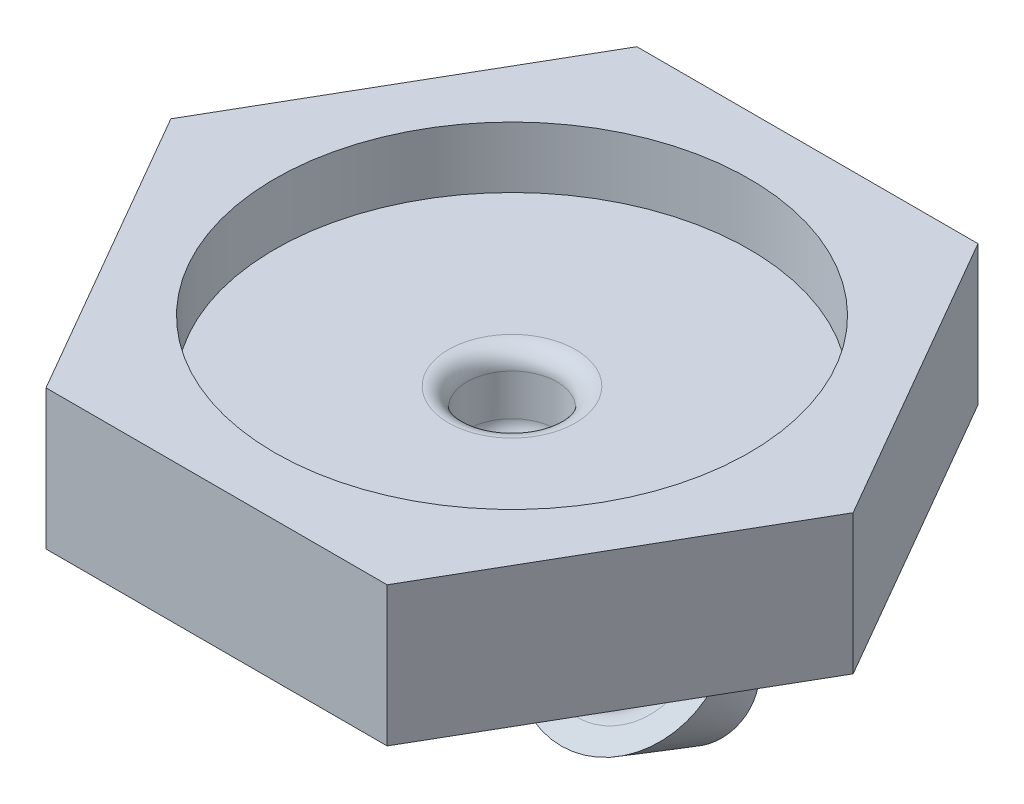
SolidWorks part; units mm, degrees
ref_plane "Front Plane" through (0, 0, 0) normal (0, 0, 1) x (1, 0, 0)
ref_plane "Top Plane" through (0, 0, 0) normal (0, 1, 0) x (1, 0, 0)
ref_plane "Right Plane" through (0, 0, 0) normal (1, 0, 0) x (0, 0, -1)
sketch "Sketch11" plane through (0, 0, 0) normal (0, 1, 0) x (1, 0, 0)
  line L7 (18.3309, 0) -> (9.1654, 15.875)
  line L8 (9.1654, 15.875) -> (-9.1654, 15.875)
  line L9 (-9.1654, 15.875) -> (-18.3309, 0)
  line L10 (-18.3309, 0) -> (-9.1654, -15.875)
  line L11 (-9.1654, -15.875) -> (9.1654, -15.875)
  line L12 (9.1654, -15.875) -> (18.3309, 0)
  circle A0 centre (0, 0) radius 15.875 construction
  dimension "D1" = 31.75
extrude "MainHolder" add sketch "Sketch11" along normal blind 7.5
sketch "Sketch12" plane through (0, 7.5, 0) normal (0, 1, 0) x (1, 0, 0)
  circle A0 centre (0, 0) radius 12.75
  dimension "D1" = 25.5
extrude "MagnetCutout" cut sketch "Sketch12" against normal blind 3.28
sketch "Sketch13" plane through (0, 4.22, 0) normal (0, 1, 0) x (1, 0, 0)
  circle A0 centre (0, 0) radius 2.415
  dimension "D1" = 4.83
extrude "MagnetHole" cut sketch "Sketch13" against normal up to next
sketch "DrainPath" plane through (0, 0, 0) normal (1, 0, 0) x (0, 0, -1)
  line L0 (0, 0) -> (0, -2)
  line L1 (1.7574, -6.2426) -> (10.2426, -14.7279)
  arc A0 (1.7574, -6.2426) -> (0, -2) centre (6, -2) cw
  point P7 (0, -4.4853)
  dimension "D3" = 6
  dimension "D1" = 135
  dimension "D2" = 12
  dimension "D4" = 2
sketch "DrainOpening" plane through (0, 0, 0) normal (0, -1, 0) x (1, 0, 0)
  circle A0 centre (0, 0) radius 1.125
  circle A2 centre (0, 0) radius 2.5
  dimension "D1" = 2.25
  dimension "D2" = 5
sweep "Drain" add profiles "DrainOpening" path "DrainPath"
ref_axis "DrainOutAxis" through (0, -5.4471, -0.9619) along (0, -0.7071, -0.7071)
ref_plane "DrainMidPlain" through (0, 0, 0) normal (-1, 0, 0) x (0, -0.7071, -0.7071)
sketch "BarbOutline" plane through (0, 0, 0) normal (-1, 0, 0) x (0, -0.7071, -0.7071)
  line L0 (17.6569, 0.6716) -> (11.6569, 0.6716)
  line L1 (11.6569, 0.6716) -> (11.6569, -1.5784)
  line L2 (11.6569, -1.5784) -> (17.6569, 0.6716)
  line L3 (5.6569, 0.6716) -> (17.6569, 0.6716) construction
  line L4 (4.5319, 3.1716) -> (18.7819, 3.1716) construction
  dimension "D1" = 6
  dimension "D2" = 4.75
revolve "Barb" add sketch "BarbOutline" angle 360 about axis through (0, -5.4471, -0.9619) along (0, -0.7071, -0.7071)
ref_axis "MagnetAxis" through (0, 0, 0) along (0, 1, 0)
fillet "DrainBaseFillet" radius 2 1 edges at (0, 0, -2.5) type face fillet first side face at (0, 0, -2.5) second side face at (0, -2, -2.5)
fillet "BarbBaseFillet" radius 1 1 edges at (0, -12.253, -4.2322) type face fillet first side face at (0, -13.844, -2.6412) second side face at (0, -12.253, -4.2322)
fillet "DrainOpenFillet" radius 1 1 edges at (0, 0, -2.415) type face fillet first side face at (0, 4.22, 2.415) second side face at (0, 0, -1.125)
fillet "MagnetFillet" radius 1 1 edges at (0, 4.22, 2.415) type face fillet first side face at (0, 4.22, 2.415) second side face at (0, 1, -2.415)
equation "\"channel_diameter\"= 4mm"
equation "\"channel_length\"= 12mm"
equation "\"barb_large_diameter\"= 4.75mm"
equation "\"barb_length\"= 6mm"
equation "\"lumen_diameter\"= 2.25mm"
equation "\"magnet_holder_thickness\" = 7.5"
equation "\"magnet_diameter\"=25.4"
equation "\"magnet_holder_tolerance\"= 0.1mm"
equation "\"magnet_thickness\"= 3.18mm"
equation "\"D1@Sketch11\"=\"magnet_diameter\" * 1.25"
equation "\"D1@MainHolder\" = \"magnet_holder_thickness\""
equation "\"D1@Sketch12\"=\"magnet_diameter\" + \"magnet_holder_tolerance\""
equation "\"D1@MagnetCutout\" = \"magnet_thickness\" + \"magnet_holder_tolerance\""
equation "\"magnet_hole_small\"= 4.83mm"
equation "\"D1@Sketch13\"=\"magnet_hole_small\""
equation "\"drain_angle\"= 135"
equation "\"D1@DrainPath\" = \"drain_angle\""
equation "\"D2@DrainPath\" = \"barb_length\" * 2"
equation "\"D1@DrainOpening\" = \"lumen_diameter\""
equation "\"D1@BarbOutline\" = \"barb_length\""
equation "\"D2@BarbOutline\"=\"barb_large_diameter\""
equation "\"FilletBase\"=3"
